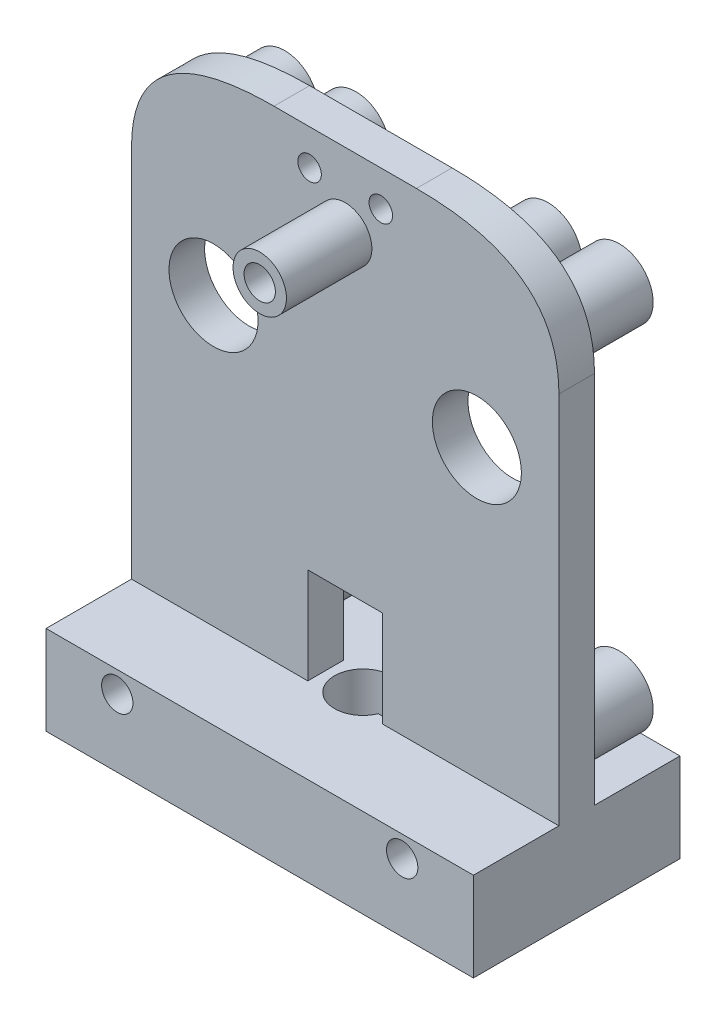
SolidWorks part; units mm, degrees
ref_plane "Ebene vorne" through (0, 0, 0) normal (0, 0, 1) x (1, 0, 0)
ref_plane "Ebene oben" through (0, 0, 0) normal (0, 1, 0) x (1, 0, 0)
ref_plane "Ebene rechts" through (0, 0, 0) normal (1, 0, 0) x (0, 0, -1)
sketch "Skizze1" plane through (0, 0, 0) normal (0, 0, 1) x (1, 0, 0)
  line L0 (-5, 35) -> (5, 35)
  line L1 (-30, -40) -> (30, -40)
  line L2 (-30, -40) -> (-30, 40)
  line L3 (-30, 40) -> (30, 40)
  line L4 (30, -40) -> (30, 40)
  line L5 (-30, -40) -> (30, 40) construction
  line L6 (-30, 40) -> (30, -40) construction
  line L7 (18.4881, 12.7723) -> (-18.4881, 12.7723)
  line L8 (-5, 35) -> (-18.4881, 12.7723)
  circle A0 centre (-5, 35) radius 1.65
  circle A1 centre (5, 35) radius 1.65
  circle A2 centre (-18.4881, 12.7723) radius 6.25
  circle A3 centre (18.4881, 12.7723) radius 6.25
  point P0 (0, 0)
  point P14 (0, 35)
  point P17 (0, 12.7723)
  dimension "D3" = 3.3
  dimension "D4" = 3.3
  dimension "D7" = 12.5
  dimension "D8" = 12.5
  dimension "D1" = 60
  dimension "D2" = 80
  dimension "D5" = 5
  dimension "D6" = 5
  dimension "D9" = 58.75
  dimension "D10" = 26
extrude "Aufsatz-Linear austragen1" add sketch "Skizze1" along normal blind 5 contours L1 L4 L3 L2 A3 A2 A1 A0 region at (0, -0.8228, 0)
sketch "Skizze2" plane through (0, 0, 5) normal (0, 0, 1) x (1, 0, 0)
  line L0 (30, -40) -> (30, 40) construction
  line L1 (-30, -40) -> (30, -40)
  line L2 (-30, -40) -> (-30, -27.5)
  line L3 (-30, -27.5) -> (30, -27.5)
  line L4 (30, -40) -> (30, -27.5)
  line L5 (-30, -40) -> (30, -27.5) construction
  line L6 (-30, -27.5) -> (30, -40) construction
  line L7 (-30, -40) -> (-30, 40) construction
  line L8 (-30, -40) -> (30, -40) construction
  point P4 (0, -33.75)
  dimension "D1" = 12.5
fillet "Verrundung1" radius 20 2 edges at (30, 40, 2.5) (-30, 40, 2.5) second distance 15 conic rho 0.5 first distance on face at (0, 40, 2.5)
extrude "Aufsatz-Linear austragen2" add sketch "Skizze2" along normal blind 12 and the other way blind 17
sketch "Skizze3" plane through (0, -40, 0) normal (0, -1, 0) x (1, 0, 0)
  line L0 (-30, 2.5) -> (30, 2.5) construction
  line L1 (-4, 2.5) -> (-4, 5.542) construction
  line L2 (2.8, 0.95) -> (5.2, 0.95)
  line L3 (2.8, 0.95) -> (2.8, 4.05)
  line L4 (2.8, 4.05) -> (5.2, 4.05)
  line L5 (5.2, 0.95) -> (5.2, 4.05)
  line L6 (2.8, 0.95) -> (5.2, 4.05) construction
  line L7 (2.8, 4.05) -> (5.2, 0.95) construction
  line L8 (-30, 17) -> (-30, -12) construction
  line L9 (30, 17) -> (30, -12) construction
  line L10 (-30, 2.5) -> (-29.124, 2.5) construction
  circle A0 centre (0, 2.5) radius 4
  point P4 (4, 2.5)
  dimension "D1" = 8
  dimension "D2" = 3.1
  dimension "D3" = 9.2
extrude "Schnitt-Linear austragen1" cut sketch "Skizze3" against normal blind 13 contours L4 A0 L2 L3 | A0 L2 L5 L4 | L2 A0 L4 L3 region at (3.3527, -40, 2.5) region at (-0.2434, -40, 2.5) region at (4.5455, -40, 2.5)
sketch "Skizze4" plane through (0, -27, 0) normal (0, -1, 0) x (1, 0, 0)
  line L1 (-5.25, -2.75) -> (5.25, -2.75)
  line L2 (-5.25, -2.75) -> (-5.25, 7.75)
  line L3 (-5.25, 7.75) -> (5.25, 7.75)
  line L4 (5.25, -2.75) -> (5.25, 7.75)
  line L5 (-5.25, -2.75) -> (5.25, 7.75) construction
  line L6 (-5.25, 7.75) -> (5.25, -2.75) construction
  arc A1 (3.6875, 4.05) -> (3.6875, 0.95) centre (0, 2.5) ccw construction
  point P0 (0, 2.5)
  point P1 (0, 2.5)
  dimension "D1" = 10.5
  dimension "D2" = 10.5
extrude "Schnitt-Linear austragen2" cut sketch "Skizze4" against normal blind 13 and the other way up to surface (0.5 mm away) other way up to face at (0, -27.5, 9.25)
sketch "Sketch1" plane through (0, 0, 5) normal (0, 0, 1) x (1, 0, 0)
  circle A0 centre (0, 29.5261) radius 3.75
  circle A1 centre (0, 29.5261) radius 2.2
  dimension "D1" = 7.5
  dimension "D2" = 4.4
extrude "Boss-Extrude1" add sketch "Sketch1" along normal blind 12
sketch "Sketch2" plane through (0, 0, 17) normal (0, 0, 1) x (1, 0, 0)
  line L0 (0, 0) -> (0, -4.9099) construction
  circle A0 centre (-20, -30.5) radius 2.2
  circle A1 centre (20, -30.5) radius 2.2
  dimension "D1" = 4.4
extrude "Cut-Extrude1" cut sketch "Sketch2" against normal blind 8
sketch "Skizze5" plane through (0, 0, 0) normal (0, 0, -1) x (-1, 0, 0)
  line L0 (-18.4881, 3.0223) -> (18.4881, 3.0223) construction
  line L1 (0, 0) -> (0, 8.9642) construction
  circle A0 centre (-23.4881, 27.7723) radius 4.75
  circle A1 centre (-13.4881, 27.7723) radius 4.75
  circle A2 centre (-23.4881, 27.7723) radius 2.7
  circle A3 centre (-13.4881, 27.7723) radius 2.7
  circle A4 centre (13.4881, 27.7723) radius 4.75
  circle A5 centre (13.4881, 27.7723) radius 2.7
  circle A6 centre (23.4881, 27.7723) radius 4.75
  circle A7 centre (23.4881, 27.7723) radius 2.7
  circle A8 centre (23.4881, -21.7277) radius 4.75
  circle A9 centre (23.4881, -21.7277) radius 2.7
  circle A10 centre (13.4881, -21.7277) radius 4.75
  circle A11 centre (13.4881, -21.7277) radius 2.7
  circle A12 centre (-13.4881, -21.7277) radius 2.7
  circle A13 centre (-13.4881, -21.7277) radius 4.75
  circle A14 centre (-23.4881, -21.7277) radius 4.75
  circle A15 centre (-23.4881, -21.7277) radius 2.7
  dimension "D1" = 9.5
  dimension "D2" = 9.5
  dimension "D3" = 5.4
  dimension "D4" = 5.4
extrude "Aufsatz-Linear austragen3" add sketch "Skizze5" along normal blind 10
